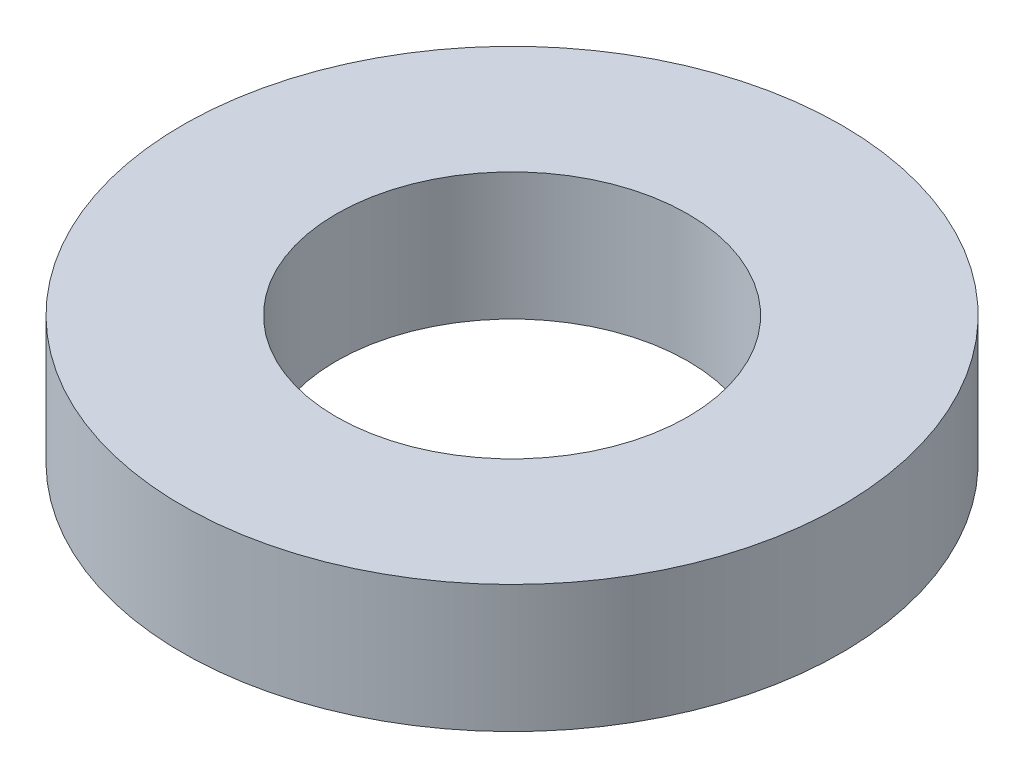
SolidWorks part; units mm, degrees
ref_plane "Front Plane" through (0, 0, 0) normal (0, 0, 1) x (1, 0, 0)
ref_plane "Top Plane" through (0, 0, 0) normal (0, 1, 0) x (1, 0, 0)
ref_plane "Right Plane" through (0, 0, 0) normal (1, 0, 0) x (0, 0, -1)
sketch "Sketch1" plane through (0, 0, 0) normal (0, 1, 0) x (1, 0, 0)
  circle A0 centre (0, 0) radius 75
  dimension "FLANGE_OD" = 150
extrude "Boss-Extrude1" add sketch "Sketch1" along normal blind 29
sketch "Sketch2" plane through (0, 0, 0) normal (0, 1, 0) x (1, 0, 0)
  circle A0 centre (0, 0) radius 40
  dimension "BORE_D" = 80
extrude "Cut-Extrude1" cut sketch "Sketch2" along normal through all
sketch "Sketch3" plane through (0, 29, 0) normal (0, 1, 0) x (1, 0, 0)
  circle A0 centre (0, 0) radius 28.5905 construction
  circle A1 centre (-28.5905, 0) radius 5.3512
  dimension "BOLT_D" = 10.7023
  dimension "BOLT_PCD" = 57.1811
extrude "Cut-Extrude2" cut sketch "Sketch3" against normal blind 24.2868 rebuild error yes
pattern_circular "CirPattern1" count 5 over 360 rebuild error yes
